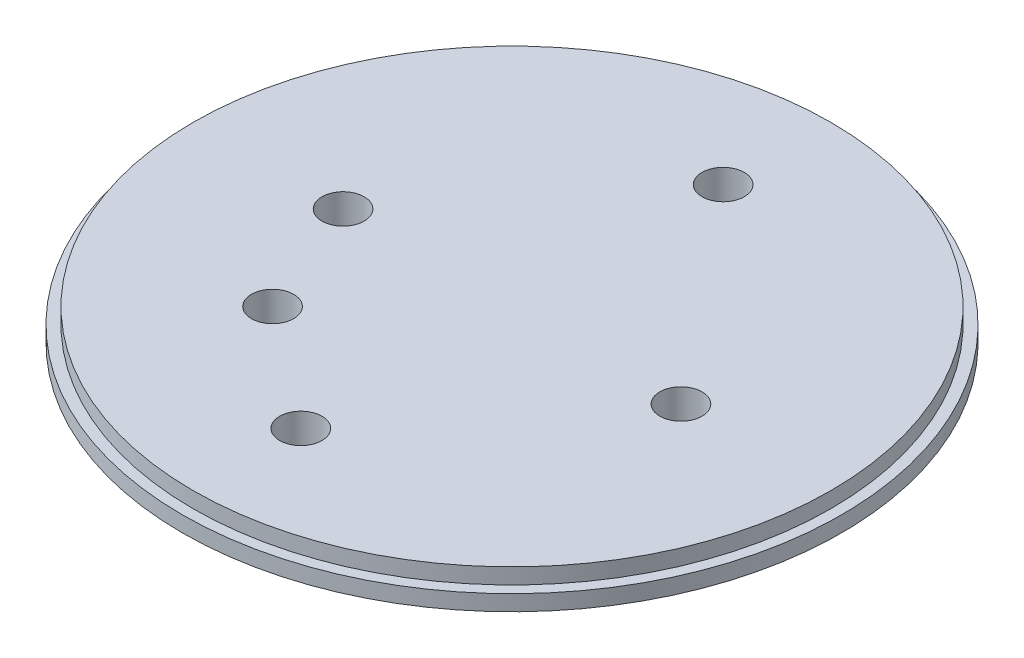
SolidWorks part; units mm, degrees
ref_plane "Front Plane" through (0, 0, 0) normal (0, 0, 1) x (1, 0, 0)
ref_plane "Top Plane" through (0, 0, 0) normal (0, 1, 0) x (1, 0, 0)
ref_plane "Right Plane" through (0, 0, 0) normal (1, 0, 0) x (0, 0, -1)
sketch "Sketch1" plane through (0, 0, 0) normal (0, 1, 0) x (1, 0, 0)
  circle A0 centre (0, 0) radius 49.55
  dimension "D1" = 99.1
extrude "Boss-Extrude1" add sketch "Sketch1" along normal blind 2.36
sketch "Sketch2" plane through (0, 2.36, 0) normal (0, 1, 0) x (1, 0, 0)
  circle A0 centre (0, 0) radius 47.95
  dimension "D1" = 95.9
extrude "Boss-Extrude2" add sketch "Sketch2" along normal blind 2.36 contours A0
sketch "Sketch3" plane through (0, 0, 0) normal (0, -1, 0) x (1, 0, 0)
  circle A0 centre (25.4, 0) radius 3.175
  circle A1 centre (-25.4, 0) radius 3.175
  circle A2 centre (0, 31.75) radius 3.175
  circle A3 centre (0, -31.75) radius 3.175
  circle A4 centre (-18, 18) radius 3.175
  dimension "D1" = 6.35
  dimension "D2" = 6.35
  dimension "D3" = 6.35
  dimension "D4" = 6.35
  dimension "D5" = 50.8
  dimension "D7" = 31.75
  dimension "D8" = 31.75
  dimension "D9" = 6.35
  dimension "D10" = 18
  dimension "D11" = 18
  dimension "D6" = 25.4
extrude "Cut-Extrude1" cut sketch "Sketch3" against normal through all
